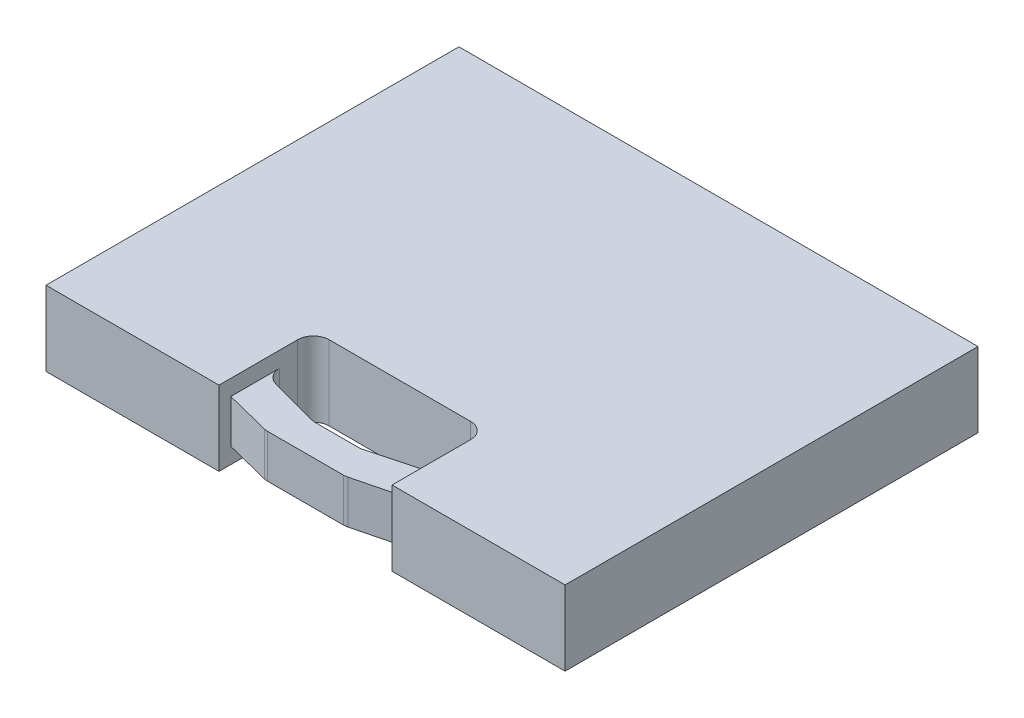
SolidWorks part; units mm, degrees
ref_plane "Front Plane" through (0, 0, 0) normal (0, 0, 1) x (1, 0, 0)
ref_plane "Top Plane" through (0, 0, 0) normal (0, 1, 0) x (1, 0, 0)
ref_plane "Right Plane" through (0, 0, 0) normal (1, 0, 0) x (0, 0, -1)
sketch "Sketch1" plane through (0, 0, 0) normal (0, 1, 0) x (1, 0, 0)
  line L1 (-209.55, -166.6875) -> (209.55, -166.6875)
  line L2 (-209.55, -166.6875) -> (-209.55, 166.6875)
  line L3 (-209.55, 166.6875) -> (209.55, 166.6875)
  line L4 (209.55, -166.6875) -> (209.55, 166.6875)
  line L5 (-209.55, -166.6875) -> (209.55, 166.6875) construction
  line L6 (-209.55, 166.6875) -> (209.55, -166.6875) construction
  point P0 (0, 0)
  dimension "D1" = 333.375
  dimension "D2" = 419.1
extrude "Boss-Extrude1" add sketch "Sketch1" along normal blind 60.325
sketch "Sketch2" plane through (0, 60.325, 0) normal (0, 1, 0) x (1, 0, 0)
  line L0 (0, 0) -> (0, -115.8875) construction
  line L1 (-69.85, -141.2875) -> (69.85, -141.2875)
  line L2 (-69.85, -141.2875) -> (-69.85, -90.4875)
  line L3 (-69.85, -90.4875) -> (69.85, -90.4875)
  line L4 (69.85, -141.2875) -> (69.85, -90.4875)
  line L5 (-69.85, -141.2875) -> (69.85, -90.4875) construction
  line L6 (-69.85, -90.4875) -> (69.85, -141.2875) construction
  line L7 (-209.55, -166.6875) -> (209.55, -166.6875) construction
  line L8 (-69.85, -166.6875) -> (-69.85, -157.1625)
  line L9 (-69.85, -157.1625) -> (-32.169, -166.6875)
  line L10 (-32.169, -166.6875) -> (-69.85, -166.6875)
  line L11 (-69.85, -157.1625) -> (-69.85, -141.2875) construction
  line L12 (0, -166.6875) -> (0, -141.2875) construction
  line L13 (69.85, -157.1625) -> (69.85, -141.2875) construction
  line L14 (32.169, -166.6875) -> (69.85, -166.6875)
  line L15 (69.85, -157.1625) -> (32.169, -166.6875)
  line L16 (69.85, -166.6875) -> (69.85, -157.1625)
  point P0 (0, -115.8875)
  dimension "D1" = 139.7
  dimension "D2" = 50.8
  dimension "D3" = 50.8
  dimension "D4" = 9.525
extrude "Cut-Extrude1" cut sketch "Sketch2" against normal through all
chamfer "Chamfer1" distance 50.8 angle 15 2 edges at (69.85, 30.1625, 141.2875) (-69.85, 30.1625, 141.2875) first distance on face at (0, 30.1625, 141.2875)
fillet "Fillet1" radius 12.7 8 edges at (32.169, 30.1625, 166.6875) (-32.169, 30.1625, 166.6875) (69.85, 30.1625, 127.6757) (19.05, 30.1625, 141.2875) (-19.05, 30.1625, 141.2875) (-69.85, 30.1625, 127.6757) (69.85, 30.1625, 90.4875) (-69.85, 30.1625, 90.4875)
sketch "Sketch3" plane through (0, 60.325, 0) normal (0, 1, 0) x (1, 0, 0)
  line L1 (-69.85, -166.6875) -> (69.85, -166.6875)
  line L2 (-69.85, -166.6875) -> (-69.85, -110.2845)
  line L3 (-69.85, -110.2845) -> (69.85, -110.2845)
  line L4 (69.85, -166.6875) -> (69.85, -110.2845)
  point P5 (0, 0)
extrude "Cut-Extrude2" cut sketch "Sketch3" against normal blind 12.7
sketch "Sketch4" plane through (0, 0, 0) normal (0, -1, 0) x (1, 0, 0)
  line L0 (69.85, 117.9306) -> (69.85, 103.1875) construction
  line L1 (-69.85, 166.6875) -> (69.85, 166.6875)
  line L2 (-69.85, 166.6875) -> (-69.85, 110.5591)
  line L3 (-69.85, 110.5591) -> (69.85, 110.5591)
  line L4 (69.85, 166.6875) -> (69.85, 110.5591)
extrude "Cut-Extrude3" cut sketch "Sketch4" against normal blind 12.7
